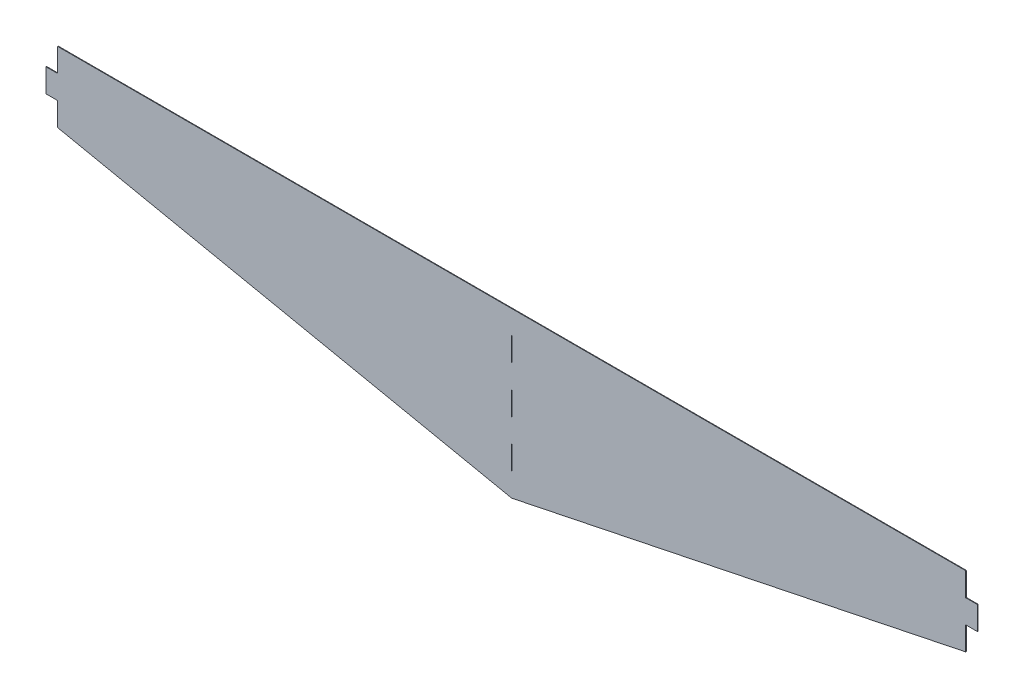
SolidWorks part; units mm, degrees
ref_plane "Front Plane" through (0, 0, 0) normal (0, 0, 1) x (1, 0, 0)
ref_plane "Top Plane" through (0, 0, 0) normal (0, 1, 0) x (1, 0, 0)
ref_plane "Right Plane" through (0, 0, 0) normal (1, 0, 0) x (0, 0, -1)
sketch "Sketch1" plane through (0, 0, 0) normal (0, 0, 1) x (1, 0, 0)
  line L0 (0, -14.5693) -> (0, 40.9289) construction
  line L1 (0, 0) -> (193.5, 40)
  line L2 (-198.5, 70) -> (-193.5, 70)
  line L3 (193.5, 70) -> (-193.5, 70)
  line L4 (193.5, 40) -> (198.5, 40)
  line L5 (198.5, 40) -> (198.5, 70)
  line L6 (198.5, 70) -> (193.5, 70)
  line L7 (-198.5, 40) -> (-198.5, 70)
  line L8 (-193.5, 40) -> (-198.5, 40)
  line L9 (0, 0) -> (-193.5, 40)
  point P13 (0, 70)
  dimension "D1" = 5
  dimension "D2" = 387
  dimension "D3" = 5
  dimension "D4" = 70
  dimension "D5" = 30
extrude "Boss-Extrude1" add sketch "Sketch1" along normal mid plane 0.25
sketch "Sketch2" plane through (0, 0, 0.125) normal (0, 0, 1) x (1, 0, 0)
  line L0 (0, 0) -> (0, 75.1617) construction
  line L1 (198.5, 70) -> (-198.5, 70) construction
  line L2 (-0.15, 60) -> (0.15, 60)
  line L3 (-0.15, 60) -> (-0.15, 50)
  line L4 (-0.15, 50) -> (0.15, 50)
  line L5 (0.15, 60) -> (0.15, 50)
  line L6 (-0.15, 60) -> (0.15, 50) construction
  line L7 (-0.15, 50) -> (0.15, 60) construction
  point P3 (0, 55)
  dimension "D1" = 10
  dimension "D2" = 10
  dimension "D3" = 0.3
extrude "Cut-Extrude1" cut sketch "Sketch2" against normal through all
pattern_linear "LPattern1" count 3 spacing 20 along (0, -1, 0) of "Cut-Extrude1"
sketch "Sketch3" plane through (0, 0, 0.125) normal (0, 0, 1) x (1, 0, 0)
  line L1 (-198.5, 70) -> (-193.5, 70)
  line L2 (-198.5, 70) -> (-198.5, 60)
  line L3 (-198.5, 60) -> (-193.5, 60)
  line L4 (-193.5, 70) -> (-193.5, 60)
  dimension "D1" = 5
  dimension "D2" = 10
extrude "Cut-Extrude2" cut sketch "Sketch3" against normal through all
pattern_linear "LPattern2" count 3 spacing 20 along (0, -1, 0) count 2 spacing 392 along (1, 0, 0) of "Cut-Extrude2"
ref_plane "ArmTopPlane" through (0, 70, 0) normal (0, 1, 0) x (1, 0, 0)
ref_axis "CenterAxis" through (0, 60, 0.125) along (0, -1, 0)
